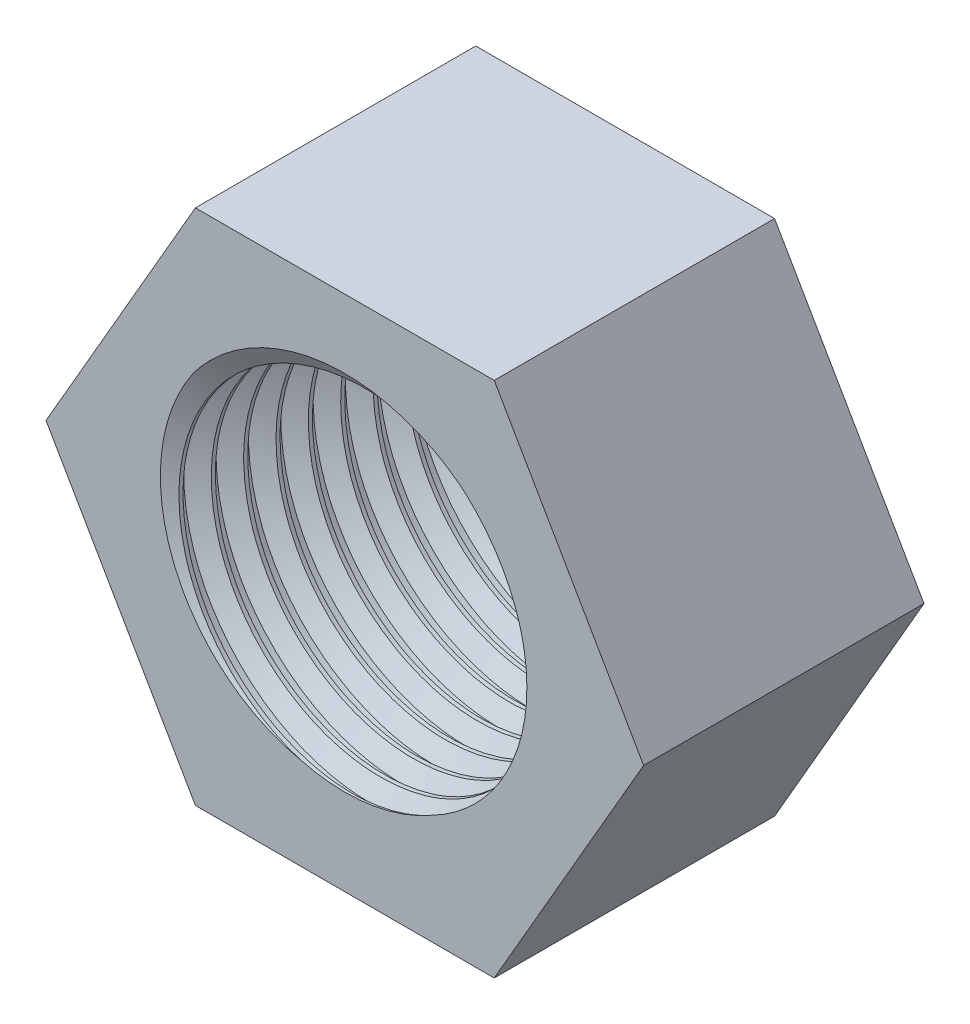
SolidWorks part; units mm, degrees
material "Gray Cast Iron"
ref_plane "Front Plane" through (0, 0, 0) normal (0, 0, 1) x (1, 0, 0)
ref_plane "Top Plane" through (0, 0, 0) normal (0, 1, 0) x (1, 0, 0)
ref_plane "Right Plane" through (0, 0, 0) normal (1, 0, 0) x (0, 0, -1)
sketch "Sketch1" plane through (0, 0, 0) normal (0, 0, 1) x (1, 0, 0)
  line L0 (0, 0) -> (-25063.0875, 0) construction
  line L1 (0, 0) -> (0, 25063.0875) construction
  line L3 (13.8564, 0) -> (6.9282, 12)
  line L4 (6.9282, 12) -> (-6.9282, 12)
  line L5 (-6.9282, 12) -> (-13.8564, 0)
  line L6 (-13.8564, 0) -> (-6.9282, -12)
  line L7 (-6.9282, -12) -> (6.9282, -12)
  line L8 (6.9282, -12) -> (13.8564, 0)
  circle A0 centre (0, 0) radius 12 construction
  circle A1 centre (0, 0) radius 8
  dimension "D1" = 24
  dimension "D2" = 16
extrude "Boss-Extrude1" add sketch "Sketch1" along normal blind 13
thread "Thread1" pitch 1.5 method cut profile "Thread Profile1" start angle 0, offset 10, length 30, pitch 1.5, diameter 16
ref_plane "Plane1" through (-8, 0, 23) normal (0, 1, 0) x (1, 0, 0)
sketch "Thread Profile1" plane through (-8, 0, 23) normal (0, 1, 0) x (1, 0, 0)
  line L0 (0, 0) -> (0, 1.5) construction
  line L11 (0, 0) -> (0, 1.3125)
  line L12 (0, 1.3125) -> (-0.8119, 0.8437)
  line L13 (-0.8119, 0.8437) -> (-0.8119, 0.4687)
  line L15 (-0.8119, 0.4687) -> (0, 0)
  line L17 (-0.8119, 0.6562) -> (0, 0.6562) construction
  point P2 (0, 0)
  dimension "Pitch" = 1.5
  dimension "Profile_Angle" = 60
  dimension "Profile_Land" = 0.375
  dimension "Profile_Height" = 0.8119
